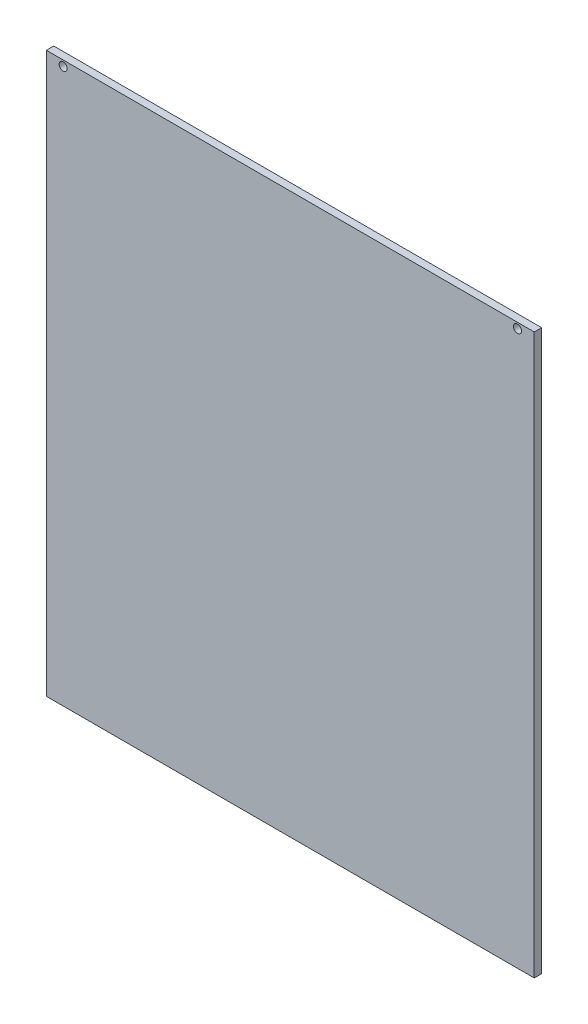
SolidWorks part; units mm, degrees
ref_plane "Front Plane" through (0, 0, 0) normal (0, 0, 1) x (1, 0, 0)
ref_plane "Top Plane" through (0, 0, 0) normal (0, 1, 0) x (1, 0, 0)
ref_plane "Right Plane" through (0, 0, 0) normal (1, 0, 0) x (0, 0, -1)
sketch "Sketch1" plane through (0, 0, 0) normal (0, 0, 1) x (1, 0, 0)
  line L0 (81.8848, 129.8822) -> (81.8848, -120.1178)
  line L1 (81.8848, 129.8822) -> (-136.1152, 129.8822)
  line L2 (81.8848, -120.1178) -> (-136.1152, -120.1178)
  line L3 (-136.1152, 129.8822) -> (-136.1152, -120.1178)
  circle A0 centre (-128.6152, 127.3822) radius 1.8
  circle A1 centre (74.3848, 127.3822) radius 1.8
  dimension "D3" = 2.5
  dimension "D1" = 250
  dimension "D2" = 218
  dimension "D4" = 7.5
  dimension "D5" = 7.5
  dimension "D6" = 2.5
extrude "Boss-Extrude1" add sketch "Sketch1" along normal blind 3.302
